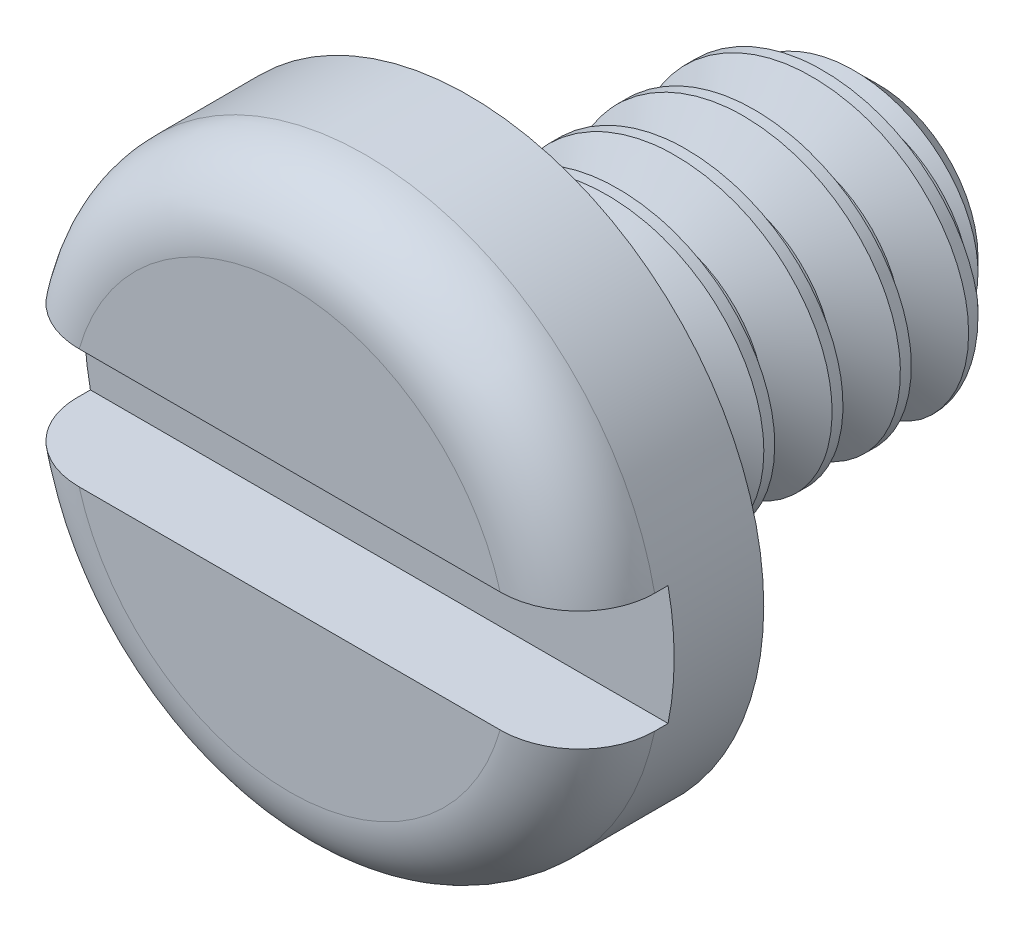
SolidWorks part; units mm, degrees
material "Nylon 6/10"
ref_plane "Front" through (0, 0, 0) normal (0, 0, 1) x (1, 0, 0)
ref_plane "Top" through (0, 0, 0) normal (0, 1, 0) x (1, 0, 0)
ref_plane "Right" through (0, 0, 0) normal (1, 0, 0) x (0, 0, -1)
sketch "Sketch1" plane through (0, 0, 0) normal (0, 0, 1) x (1, 0, 0)
  circle A0 centre (0, 0) radius 3.429
  dimension "Head Dia" = 6.858
extrude "Extrude3" add sketch "Sketch1" along normal blind 2.0828
sketch "Sketch11" plane through (0, 0, 0) normal (1, 0, 0) x (0, 0, -1)
  line L0 (0, 0) -> (-2.3368, 0) construction
  line L1 (-2.0828, 2.5438) -> (-2.0828, 0)
  line L4 (-2.0828, 3.429) -> (-2.0828, -3.429) construction
  line L5 (-2.3368, 3.5662) -> (0, 3.5662)
  line L7 (0, 3.5662) -> (0, 3.429)
  line L8 (-1.1976, 3.429) -> (0, 3.429)
  line L9 (0, -3.429) -> (0, 3.429) construction
  line L11 (0, 3.429) -> (-2.0828, 3.429) construction
  line L13 (-2.0828, 0) -> (-2.3368, 0)
  line L14 (-2.3368, 0) -> (-2.3368, 3.5662)
  arc A2 (-2.0828, 2.5438) -> (-1.1976, 3.429) centre (-1.1976, 2.5438) cw
  dimension "D4" = 0.8852
  dimension "D3" = 0.254
  dimension "D5" = 0.1372
revolve "Cut-Revolve3" cut sketch "Sketch11" angle 360 about L0
sketch "Sketch4" plane through (0, 0, 0) normal (1, 0, 0) x (0, 0, -1)
  line L0 (0, 0) -> (4.7625, 0)
  line L3 (4.7625, 0) -> (4.7625, 1.7526)
  line L4 (4.7625, 1.7526) -> (0, 1.7526)
  line L6 (0, 1.7526) -> (0, 0)
  line L9 (4.7625, 1.7526) -> (4.7625, -1.7526) construction
  dimension "length" = 4.7625
  dimension "dia" = 3.5052
revolve "Revolve1" add sketch "Sketch4" angle 360 about L0
sketch "Sketch13" plane through (0, 0, -4.7625) normal (0, 0, -1) x (-1, 0, 0)
  circle A2 centre (0, 0) radius 1.7526
curve "Helix/Spiral1" pitch 0.7937 height 6.8453 radius 1.7526 centre (0, 0, -4.7625) axis (0, 0, 1) start towards (1, 0, 0)
chamfer "Chamfer2" distance 0.5953 angle 45 1 edges at (1.7526, 0, -4.7625)
sketch "Sketch14" plane through (0, 0, 0) normal (1, 0, 0) x (0, 0, -1)
  line L0 (4.7625, 1.7774) -> (5.457, 1.7774)
  line L1 (5.457, 1.7774) -> (5.1594, 1.2404)
  line L2 (5.1594, 1.2404) -> (5.0602, 1.2404)
  line L3 (5.0602, 1.2404) -> (4.7625, 1.7774)
  line L4 (4.9113, 1.5089) -> (5.3082, 1.5089) construction
  dimension "D1" = 0.0992
  dimension "D2" = 58
  dimension "D3" = 0.3969
  dimension "D4" = 0.0248
sweep "Cut-Sweep1" cut profiles "Sketch14" path "Helix/Spiral1" align with end faces yes
ref_plane "Plane1" through (0, 0, 33.3375) normal (0, 0, -1) x (-1, 0, 0)
sketch "Sketch29" [suppressed] plane through (0, 0, 28.575) normal (0, 0, -1) x (-1, 0, 0)
  circle A0 centre (0, 0) radius 1.7526 construction
  circle A1 centre (0, 0) radius 1.7526
  point P3 (0, -1.7526)
  point P4 (0, 1.7526)
extrude "Extrude11" [suppressed] add sketch "Sketch29" against normal up to surface (28.575 mm away) up to plane "Front"
sketch "Sketch26" plane through (0, 0, 0) normal (0, 0, 1) x (1, 0, 0)
  circle A1 centre (0, 0) radius 0.5461
  dimension "D1" = 1.0922
extrude "Extrude13" add sketch "Sketch26" along normal up to surface (2.0828 mm away) up to face at (0, 2.5438, 2.0828)
sketch "Sketch31" plane through (0, 0, 2.0828) normal (0, 0, 1) x (1, 0, 0)
  line L0 (-3.429, 0.6945) -> (3.429, -0.6945) construction
  line L1 (-3.429, 0.6945) -> (3.429, 0.6945)
  line L2 (-3.429, 0.6945) -> (-3.429, -0.6945)
  line L3 (-3.429, -0.6945) -> (3.429, -0.6945)
  line L4 (3.429, 0.6945) -> (3.429, -0.6945)
  circle A0 centre (0, 0) radius 3.429 construction
  dimension "D1" = 1.3891
extrude "Extrude15" cut sketch "Sketch31" against normal blind 1.0414
sketch "Sketch18" plane through (0, 0, 0) normal (1, 0, 0) x (0, 0, -1)
  line L1 (4.7625, 1.7526) -> (0, 1.7526) construction
  point P0 (3.5719, -1.7526)
  point P1 (3.9688, 1.7526)
  point P2 (-2.0828, 2.5438)
  dimension "D1" = 0.7937
  dimension "D2" = 1.1906
equation "\"D3@Helix/Spiral1\" = \"length@Sketch4\" + \"Head Ht@Extrude3\""
equation "\"D1@Sketch14\" = \"D4@Helix/Spiral1\" * .125"
equation "\"D3@Sketch14\" = \"D4@Helix/Spiral1\" * .5"
equation "\"D5@Sketch11\" = \"Head Dia@Sketch1\" * .02"
equation "\"D4@Sketch14\" = \"D1@Sketch14\" * .25"
equation "\"D1@Chamfer2\" = \"D4@Helix/Spiral1\" * .75"
equation "\"D1@Sketch18\" = \"D4@Helix/Spiral1\""
equation "\"D2@Sketch18\" = \"D4@Helix/Spiral1\" * 1.5"
equation "\"D1@Extrude15\" = \"Head Ht@Extrude3\" * .5"
equation "\"D4@Sketch11\" = \"Head Ht@Extrude3\" * .425"
equation "\"D1@Sketch31\" = \"D4@Helix/Spiral1\" * 1.75"
